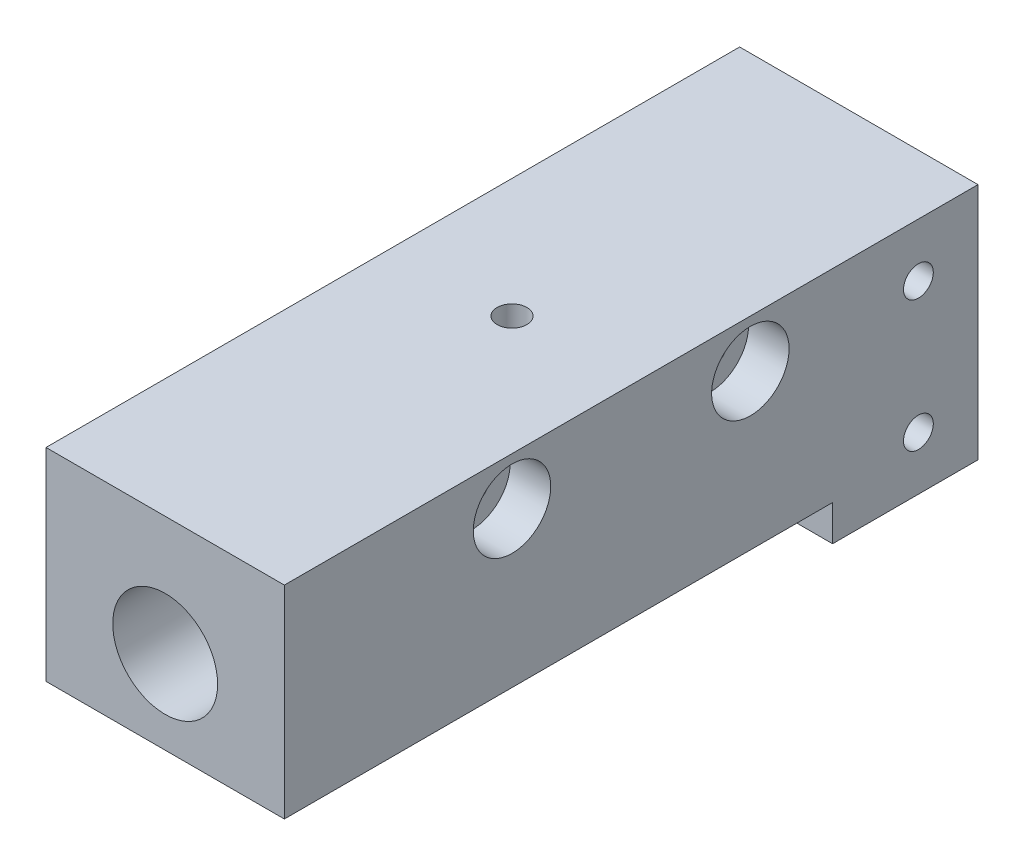
SolidWorks part; units mm, degrees
material "6063-T5"
ref_plane "Piano frontale" through (0, 0, 0) normal (0, 0, 1) x (1, 0, 0)
ref_plane "Piano superiore" through (0, 0, 0) normal (0, 1, 0) x (1, 0, 0)
ref_plane "Piano destro" through (0, 0, 0) normal (1, 0, 0) x (0, 0, -1)
sketch "Schizzo1" plane through (0, 0, 0) normal (0, 0, 1) x (1, 0, 0)
  line L1 (10, -10) -> (-10, -10)
  line L2 (10, -10) -> (10, 10)
  line L3 (10, 10) -> (-10, 10)
  line L4 (-10, -10) -> (-10, 10)
  line L5 (10, -10) -> (-10, 10) construction
  line L6 (10, 10) -> (-10, -10) construction
  point P0 (0, 0)
  dimension "D1" = 20
  dimension "D2" = 20
extrude "Estrusione-Estrusione1" add sketch "Schizzo1" against normal blind 58.2
sketch "Schizzo2" plane through (0, 0, -58.2) normal (0, 0, -1) x (-1, 0, 0)
  circle A0 centre (0, 0) radius 3
  dimension "D1" = 6
extrude "Taglio-Estrusione1" cut sketch "Schizzo2" against normal through all
sketch "Schizzo3" plane through (0, 0, -58.2) normal (0, 0, -1) x (-1, 0, 0)
  point P0 (0, 0)
sketch "Schizzo4" plane through (10, 0, 0) normal (1, 0, 0) x (0, 0, -1)
  line L0 (0, 6) -> (58.2, 6) construction
  line L1 (0, -10) -> (0, 10) construction
  line L2 (58.2, -10) -> (58.2, 10) construction
  line L3 (58.2, 10) -> (0, 10) construction
  line L4 (29.1, 10) -> (29.1, -10) construction
  line L5 (58.2, -10) -> (0, -10) construction
  point P12 (39.1, 6)
  point P17 (19.1, 6)
  dimension "D2" = 20
  dimension "D1" = 4
hole_wizard "Foro filettato G1/8-1" positions "Schizzo8" profile "Schizzo7" tap size "G1/8" standard "BSI"
sketch "Schizzo8" plane through (0, 0, 0) normal (0, 0, 1) x (1, 0, 0)
  point P0 (0, 0)
sketch "Schizzo7" plane through (0, 0, 0) normal (1, 0, 0) x (0, -1, 0)
  line L0 (0, 0) -> (0, 12.6438)
  line L1 (0, 12.6438) -> (4.4, 10)
  line L2 (4.4, 10) -> (4.4, 0)
  line L5 (4.4, 0) -> (0, 0)
  line L10 (0, 12.6438) -> (-4.4, 10) construction
  line L11 (0, -6.35) -> (0, 107.95) construction
  dimension "Tap Drill Dia." = 8.8
  dimension "Tap Drill Depth" = 10
  dimension "Drill Angle" = 118
sketch "Schizzo10" plane through (10, 0, 0) normal (1, 0, 0) x (0, 0, -1)
  line L0 (0, -7) -> (46, -7)
  line L1 (0, -10) -> (0, 10) construction
  line L2 (46, -7) -> (46, -10)
  line L3 (58.2, -10) -> (0, -10) construction
  dimension "D1" = 46
  dimension "D2" = 3
extrude "Taglio-Estrusione5" cut sketch "Schizzo10" against normal through all and the other way through all flip side to cut
sketch "Schizzo11" plane through (0, 10, 0) normal (0, 1, 0) x (1, 0, 0)
  line L0 (0, 58.2) -> (0, 0) construction
  line L1 (10, 58.2) -> (-10, 58.2) construction
  line L2 (10, 29.1) -> (-10, 29.1) construction
  line L3 (10, 58.2) -> (10, 0) construction
  point P10 (0, 29.1)
  point P11 (0, 29.1)
  point P12 (0, 29.1)
hole_wizard "Foro filettato M3-1" positions "Schizzo3D1" profile "Schizzo12" tap size "M3" standard "DIN"
sketch3d "Schizzo3D1"
  point P0 (0, 10, -29.1)
sketch "Schizzo12" plane through (0, 10, -29.1) normal (1, 0, 0) x (0, 0, 1)
  line L0 (0, 0) -> (0, 5.7511)
  line L1 (0, 5.7511) -> (1.25, 5)
  line L2 (1.25, 5) -> (1.25, 0)
  line L5 (1.25, 0) -> (0, 0)
  line L10 (0, 5.7511) -> (-1.25, 5) construction
  line L11 (0, -6.35) -> (0, 107.95) construction
  dimension "Tap Drill Dia." = 2.5
  dimension "Tap Drill Depth" = 5
  dimension "Drill Angle" = 118
hole_wizard "Foro Ø16.0 (16)-1" positions "Schizzo3D3" profile "Schizzo14" hole size "Ø16.0" standard "ISO"
sketch3d "Schizzo3D3"
  point P0 (0, 0, 0)
  point P3 (0, 0, -58.2)
sketch "Schizzo14" plane through (0, 0, -58.2) normal (1, 0, 0) x (0, 1, 0)
  line L0 (0, 0) -> (0, 16.8069)
  line L1 (0, 16.8069) -> (8, 12)
  line L2 (8, 12) -> (8, 0)
  line L5 (8, 0) -> (0, 0)
  line L10 (0, 16.8069) -> (-8, 12) construction
  line L11 (0, -6.35) -> (0, 107.95) construction
  dimension "Hole Dia." = 16
  dimension "Hole Depth" = 12
  dimension "Drill Angle" = 118
sketch "Schizzo15" plane through (10, 0, 0) normal (1, 0, 0) x (0, 0, -1)
  line L0 (46.2, 0) -> (58.2, 0) construction
  line L1 (46.2, 8) -> (46.2, -8) construction
  line L4 (58.2, -10) -> (58.2, 10) construction
  line L6 (58.2, -10) -> (46, -10) construction
  point P5 (53.2, -5.5)
  point P8 (53.2, 5.5)
  dimension "D1" = 5.5
  dimension "D2" = 7
  dimension "D3" = 5
  dimension "D4" = 4.5
hole_wizard "Foro filettato M3-2" positions "Schizzo3D4" profile "Schizzo16" tap size "M3" standard "ISO" end condition through all
sketch3d "Schizzo3D4"
  point P0 (10, 5.5, -53.2)
  point P3 (10, -5.5, -53.2)
sketch "Schizzo16" plane through (10, 5.5, -53.2) normal (0, 1, 0) x (0, 0, -1)
  line L0 (0, 0) -> (0, 20)
  line L1 (0, 20) -> (1.25, 20)
  line L2 (1.25, 20) -> (1.25, 0)
  line L5 (1.25, 0) -> (0, 0)
  line L11 (0, -6.35) -> (0, 107.95) construction
  dimension "Thread Major Dia." = 2.5
  dimension "Thru Tap Drill Depth" = 20
hole_wizard "CBORE for M3 Hex Socket Head Cap Screw1" positions "3DSketch5" profile "Sketch4" counterbore size "M3" standard "ISO" end condition through all
sketch3d "3DSketch5"
  point P0 (10, 6, -19.1)
  point P4 (10, 6, -39.1)
sketch "Sketch4" plane through (10, 6, -19.1) normal (0, 1, 0) x (0, 0, -1)
  line L0 (0, 0) -> (0, 20)
  line L1 (0, 20) -> (1.6, 20)
  line L3 (1.6, 20) -> (1.6, 3.4)
  line L4 (1.6, 3.4) -> (3.25, 3.4)
  line L5 (3.25, 3.4) -> (3.25, 0)
  line L7 (3.25, 0) -> (0, 0)
  line L11 (0, -6.35) -> (0, 107.95) construction
  dimension "Thru Hole Dia." = 3.2
  dimension "Thru Hole Depth" = 20
  dimension "C'Bore Dia." = 6.5
  dimension "C'Bore Depth" = 3.4
